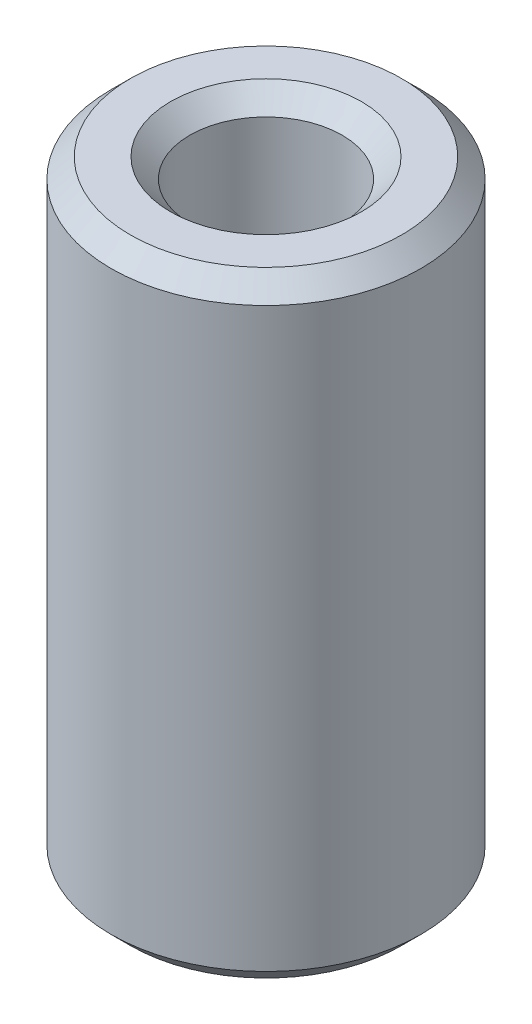
SolidWorks part; units mm, degrees
ref_plane "Front Plane" through (0, 0, 0) normal (0, 0, 1) x (1, 0, 0)
ref_plane "Top Plane" through (0, 0, 0) normal (0, 1, 0) x (1, 0, 0)
ref_plane "Right Plane" through (0, 0, 0) normal (1, 0, 0) x (0, 0, -1)
sketch "Sketch1" plane through (0, 0, 0) normal (0, 1, 0) x (1, 0, 0)
  circle A0 centre (0, 0) radius 7.5
  dimension "SLEEVE_OD" = 15
extrude "Boss-Extrude1" add sketch "Sketch1" along normal blind 29.7884
sketch "Sketch2" plane through (0, 0, 0) normal (0, 1, 0) x (1, 0, 0)
  circle A0 centre (0, 0) radius 3.6844
  dimension "BORE_D" = 7.3687
extrude "Cut-Extrude1" cut sketch "Sketch2" along normal through all
chamfer "Chamfer1" distance 0.9374 angle 45 4 edges at (0, 29.7884, 3.6844) (0, 0, 3.6844) (0, 0, 7.5) (0, 29.7884, 7.5)
